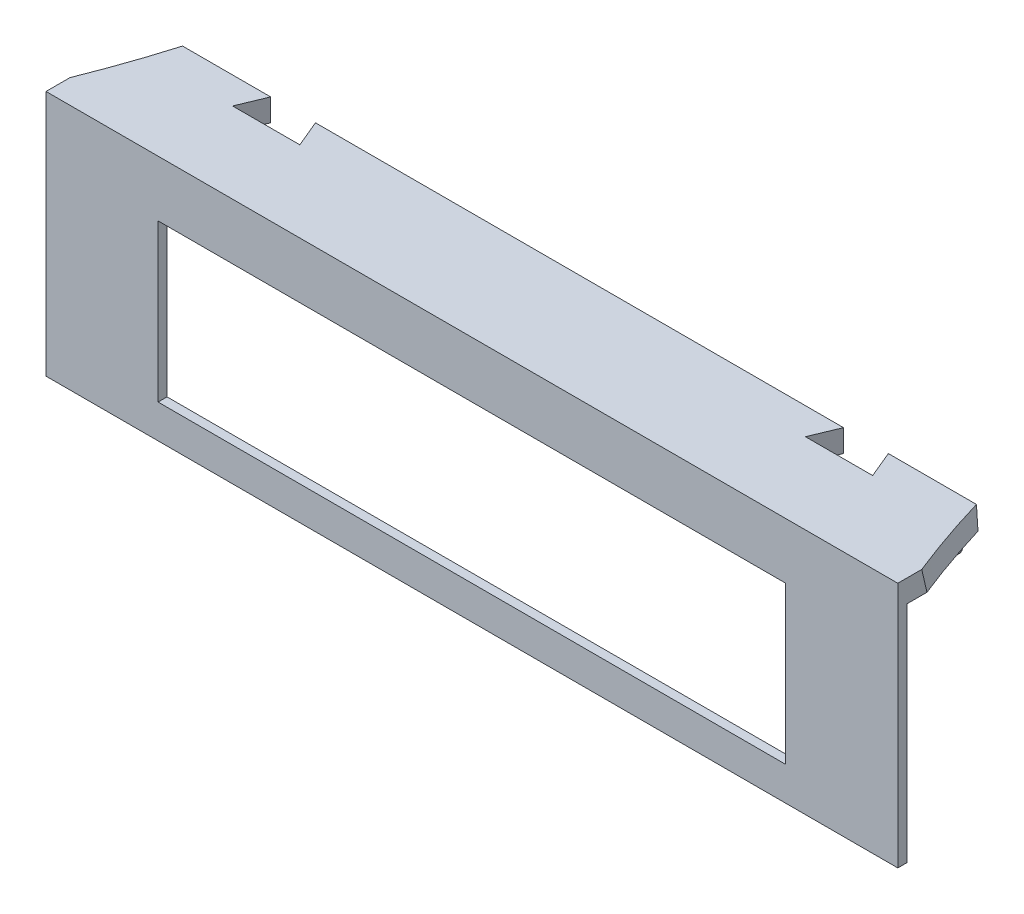
SolidWorks part; units mm, degrees
ref_plane "Front Plane" through (0, 0, 0) normal (0, 0, 1) x (1, 0, 0)
ref_plane "Top Plane" through (0, 0, 0) normal (0, 1, 0) x (1, 0, 0)
ref_plane "Right Plane" through (0, 0, 0) normal (1, 0, 0) x (0, 0, -1)
sketch "Sketch1" plane through (0, 0, 0) normal (0, 0, 1) x (1, 0, 0)
  line L1 (95, -25) -> (-95, -25)
  line L2 (95, -25) -> (95, 25)
  line L3 (95, 25) -> (-95, 25)
  line L4 (-95, -25) -> (-95, 25)
  line L5 (95, -25) -> (-95, 25) construction
  line L6 (95, 25) -> (-95, -25) construction
  line L7 (70, -17.5) -> (-70, -17.5)
  line L8 (70, -17.5) -> (70, 17.5)
  line L9 (70, 17.5) -> (-70, 17.5)
  line L10 (-70, -17.5) -> (-70, 17.5)
  line L11 (70, -17.5) -> (-70, 17.5) construction
  line L12 (70, 17.5) -> (-70, -17.5) construction
  point P0 (0, 0)
  point P5 (0, 0)
  dimension "D1" = 190
  dimension "D2" = 50
  dimension "D3" = 35
  dimension "D4" = 140
extrude "Boss-Extrude1" add sketch "Sketch1" along normal blind 2
sketch "Sketch3" plane through (0, 0, 2) normal (0, 0, 1) x (1, 0, 0)
  line L0 (95, -25) -> (95, 25) construction
  line L1 (-95, 25) -> (95, 25)
  line L2 (-95, 25) -> (-95, 30)
  line L3 (-95, 30) -> (95, 30)
  line L4 (95, 25) -> (95, 30)
  dimension "D1" = 5
extrude "Boss-Extrude2" add sketch "Sketch3" against normal blind 24
sketch "Sketch6" plane through (-95, 0, 0) normal (-1, 0, 0) x (0, 0, 1)
  line L0 (-22, 25) -> (0, 25) construction
  line L1 (-20, 25) -> (-15, 25)
  line L2 (-20, 25) -> (-20, 19.75)
  line L3 (-20, 19.75) -> (-15, 19.75)
  line L4 (-15, 25) -> (-15, 19.75)
  line L5 (-22, 30) -> (-22, 25) construction
  dimension "D1" = 5.25
  dimension "D2" = 2
  dimension "D3" = 5
extrude "Boss-Extrude3" add sketch "Sketch6" against normal blind 5.25 from offset 7.5 offset against normal yes
ref_plane "Plane1" through (0, 18.8395, 4.3968) normal (0, 0.9738, 0.2273) x (1, 0, 0)
sketch "Sketch5" plane through (0, 18.8395, 4.3968) normal (0, 0.9738, 0.2273) x (1, 0, 0)
  line L0 (95, 28.2425) -> (88.5411, 28.2425)
  line L2 (95, 28.2425) -> (-95, 28.2425) construction
  line L3 (95, 28.2425) -> (95, 10.0682)
  line L4 (95, 27.1061) -> (95, 5.6818) construction
  arc A1 (81.8135, 59.2113) -> (83.6925, 47.8197) centre (280.0044, 86.0509) ccw construction
  arc A2 (95, 10.0682) -> (88.5411, 28.2425) centre (280.0044, 86.0509) cw
extrude "Cut-Extrude1" cut sketch "Sketch5" against normal through all both and the other way through all
mirror "Mirror1" about plane through (0, 0, 0) normal (1, 0, 0) of "Cut-Extrude1"
sketch "Sketch7" plane through (0, 0, -20) normal (0, 0, -1) x (-1, 0, 0)
  line L0 (88.8879, 25) -> (-88.8879, 25) construction
  line L1 (87.5, 25) -> (87.5, 19.75) construction
  circle A0 centre (84.875, 22.375) radius 2.625 construction
  circle A1 centre (84.875, 22.375) radius 1.65
  dimension "D1" = 3.3
  dimension "D2" = 5.25
extrude "Cut-Extrude2" cut sketch "Sketch7" against normal up to surface (5 mm away) up to face at (-84.875, 22.375, -15)
fillet "Fillet1" radius 2.75 2 edges at (-87.5, 19.75, -17.5) (-82.25, 19.75, -17.5)
mirror "Mirror3" about plane through (0, 0, 0) normal (1, 0, 0) of "Boss-Extrude3", "Fillet1", "Cut-Extrude2"
sketch "Sketch9" plane through (0, 25, 0) normal (0, -1, 0) x (1, 0, 0)
  line L0 (-68.8879, -22) -> (-71.3879, -16)
  line L1 (-88.8879, -22) -> (88.8879, -22) construction
  line L2 (-71.3879, -16) -> (-56.3879, -16)
  line L3 (-56.3879, -16) -> (-58.8879, -22)
  line L4 (-58.8879, -22) -> (-68.8879, -22)
  dimension "D1" = 20
  dimension "D2" = 10
  dimension "D3" = 15
  dimension "D4" = 6
extrude "Cut-Extrude3" cut sketch "Sketch9" against normal up to surface (5 mm away) up to face at (0, 30, -7.7524)
mirror "Mirror4" about plane through (0, 0, 0) normal (1, 0, 0) of "Cut-Extrude3"
sketch "Sketch10" plane through (0, 0, 0) normal (0, 0, -1) x (-1, 0, 0)
  line L0 (88.8879, 25) -> (68.8879, 25) construction
  line L1 (81.875, 25) -> (87.875, 25)
  line L2 (81.875, 25) -> (81.875, 19)
  line L3 (81.875, 19) -> (87.875, 19)
  line L4 (87.875, 25) -> (87.875, 19)
  point P6 (84.875, 25)
  dimension "D1" = 6
  dimension "D2" = 6
extrude "Cut-Extrude4" cut sketch "Sketch10" against normal blind 1.6
chamfer "Chamfer1" distance 1 angle 45 3 edges at (-81.875, 22, 0) (-87.875, 22, 0) (-84.875, 19, 0)
sketch "Sketch12" plane through (0, 0, 0) normal (0, 0, -1) x (-1, 0, 0)
  line L0 (95, -25) -> (-95, -25) construction
  line L1 (-87.875, -25) -> (-81.875, -25)
  line L2 (-87.875, -25) -> (-87.875, -19)
  line L3 (-87.875, -19) -> (-81.875, -19)
  line L4 (-81.875, -25) -> (-81.875, -19)
  line L7 (-84.875, 22.375) -> (-84.875, -36.5451) construction
  point P9 (-84.875, -19)
  dimension "D1" = 6
  dimension "D2" = 6
extrude "Cut-Extrude5" cut sketch "Sketch12" against normal blind 1.6
mirror "Mirror5" about plane through (0, 0, 0) normal (1, 0, 0) of "Cut-Extrude5", "Chamfer1", "Cut-Extrude4"
